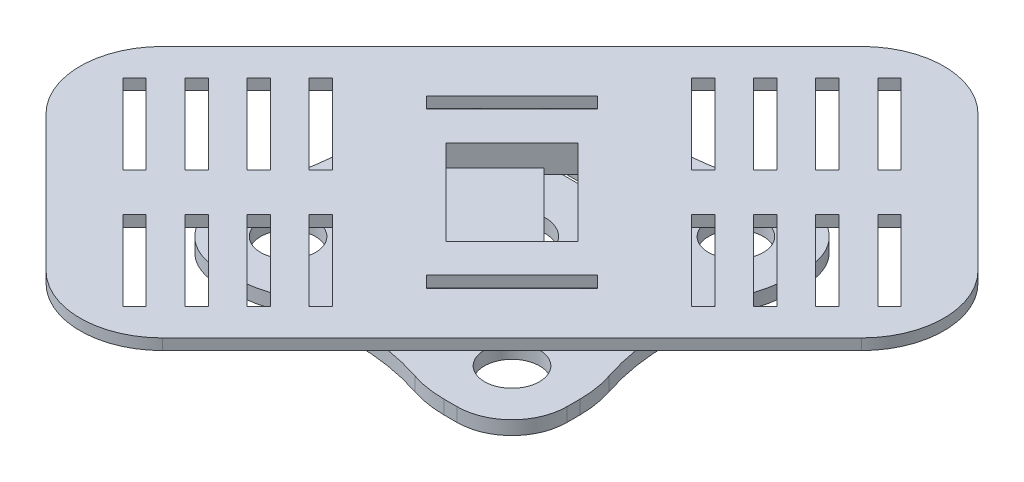
SolidWorks part; units mm, degrees
note: '?' marks a value the reader was unsure of.
ref_plane "Front" through (0, 0, 0) normal (0, 0, 1) x (1, 0, 0)
ref_plane "Top" through (0, 0, 0) normal (0, 1, 0) x (1, 0, 0)
ref_plane "Right" through (0, 0, 0) normal (1, 0, 0) x (0, 0, -1)
sketch "草图1" plane through (0, 0, 0) normal (0, 1, 0) x (1, 0, 0)
  line L0 (0, 24.7487) -> (0, 0) construction
  line L1 (31.8198, -31.8198) -> (15.8406, -31.8198)
  line L2 (31.8198, -31.8198) -> (31.8198, -15.8406)
  line L3 (31.8198, 31.8198) -> (15.8406, 31.8198)
  line L4 (-31.8198, -31.8198) -> (-31.8198, -15.8406)
  line L5 (31.8198, -31.8198) -> (-31.8198, 31.8198) construction
  line L6 (31.8198, 31.8198) -> (-31.8198, -31.8198) construction
  line L7 (0, 24.7487) -> (0, 70.2543) construction
  line L8 (-31.8198, 15.8406) -> (-31.8198, 31.8198)
  line L9 (31.8198, 15.8406) -> (31.8198, 31.8198)
  line L10 (-15.8406, -31.8198) -> (-31.8198, -31.8198)
  line L11 (-15.8406, 31.8198) -> (-31.8198, 31.8198)
  arc A0 (-15.8406, 31.8198) -> (15.8406, 31.8198) centre (0, 70.2543) ccw
  arc A1 (31.8198, 15.8406) -> (31.8198, -15.8406) centre (70.2543, 0) ccw
  arc A2 (15.8406, -31.8198) -> (-15.8406, -31.8198) centre (0, -70.2543) ccw
  arc A3 (-31.8198, -15.8406) -> (-31.8198, 15.8406) centre (-70.2543, 0) ccw
  point P0 (0, 0)
  point P23 (0, 0)
  dimension "D1" = 4
extrude "凸台-拉伸1" add sketch "草图1" along normal blind 2.5
fillet "圆角1" radius 10 1 edges at (31.8198, 1.25, 31.8198)
ref_axis "基准轴1" through (0, 27.9421, 0) along (0, 1, 0)?
fillet "圆角2" radius 10 1 edges at (31.8198, 1.25, -31.8198)
fillet "圆角3" radius 10 1 edges at (-31.8198, 1.25, -31.8198)
fillet "圆角4" radius 10 1 edges at (-31.8198, 1.25, 31.8198)
sketch "草图2" plane through (0, 2.5, 0) normal (0, 1, 0) x (1, 0, 0)
  line L0 (-31.8198, 15.8406) -> (-15.8406, 31.8198) construction
  line L1 (15.8406, -31.8198) -> (31.8198, -15.8406) construction
  line L2 (23.8302, -23.8302) -> (-23.8302, 23.8302) construction
  line L3 (-20.3878, 20.3878) -> (-15.8406, 31.8198) construction
  line L4 (-20.3878, 20.3878) -> (-31.8198, 15.8406) construction
  line L5 (-31.8198, 15.8406) -> (-23.8302, 23.8302) construction
  line L6 (-34.8639, 27.7928) -> (-27.7928, 34.8639) construction
  line L7 (15.8406, 31.8198) -> (-15.8406, 31.8198) construction
  line L12 (0, 31.8198) -> (0, 0) construction
  line L13 (-20.3878, 20.3878) -> (31.8198, 15.8406) construction
  line L14 (-50.7807, 30.9679) -> (-32.266, 49.4825) construction
  line L15 (7.5, 17.2523) -> (-7.5, 17.2523)
  line L16 (7.5, 17.2523) -> (7.5, 14.3647)
  line L17 (7.5, 14.3647) -> (-7.5, 14.3647)
  line L18 (-7.5, 17.2523) -> (-7.5, 14.3647)
  line L19 (7.5, 17.2523) -> (-7.5, 14.3647) construction
  line L20 (7.5, 14.3647) -> (-7.5, 17.2523) construction
  line L21 (-27.7928, 34.8639) -> (-46.8847, 53.9557) construction
  line L22 (-31.3283, 31.3283) -> (0, 0) construction
  line L23 (0, 0) -> (3.5355, 3.5355) construction
  circle A2 centre (-20.3878, 20.3878) radius 5
  circle A3 centre (-46.8847, 53.9557) radius 1.52
  circle A4 centre (-53.9557, 46.8847) radius 1.52
  point P11 (-31.3283, 31.3283)
  point P19 (0, 15.8085)
  dimension "D1" = 44.3049
  dimension "D2" = 28.8327
extrude "切除-拉伸1" cut sketch "草图2" against normal blind 49
fillet "圆角5" radius 20 1 edges at (-15.8406, 1.25, -31.8198)
fillet "圆角6" radius 20 1 edges at (-31.8198, 1.25, -15.8406)
pattern_circular "阵列(圆周)2" count 4 every 90 about axis through (0, 0, 0) along (0, 1, 0) of "切除-拉伸1"
sketch "草图3" plane through (0, 2.5, 0) normal (0, 1, 0) x (1, 0, 0)
  circle A0 centre (0, 0) radius 6
extrude "切除-拉伸2" cut sketch "草图3" against normal blind 49 and the other way blind 85
sketch "草图4" plane through (0, 2.5, 0) normal (0, 1, 0) x (1, 0, 0)
fillet "圆角7" radius 20 1 edges at (31.8198, 1.25, 15.8406)
fillet "圆角8" radius 20 1 edges at (15.8406, 1.25, 31.8198)
fillet "圆角9" radius 20 1 edges at (-31.8198, 1.25, 15.8406)
fillet "圆角10" radius 20 1 edges at (-15.8406, 1.25, 31.8198)
fillet "圆角11" radius 20 1 edges at (15.8406, 1.25, -31.8198)
fillet "圆角12" radius 20 1 edges at (31.8198, 1.25, -15.8406)
ref_plane "基准面1" through (0, 7.5, 0) normal (0, 1, 0) x (1, 0, 0)
sketch "草图5" plane through (0, 7.5, 0) normal (0, 1, 0) x (1, 0, 0)
  line L1 (65.4074, 19.4454) -> (19.4454, 65.4074)
  line L2 (65.4074, 19.4454) -> (-19.4454, -65.4074)
  line L3 (-19.4454, -65.4074) -> (-65.4074, -19.4454)
  line L4 (19.4454, 65.4074) -> (-65.4074, -19.4454)
  line L5 (65.4074, 19.4454) -> (-65.4074, -19.4454) construction
  line L6 (-19.4454, -65.4074) -> (19.4454, 65.4074) construction
  point P0 (0, 0)
extrude "凸台-拉伸2" add sketch "草图5" along normal blind 2 separate body contours L1 L4 L3 L2
sketch "草图6" plane through (0, 7.5, 0) normal (0, 1, 0) x (1, 0, 0)
  line L0 (-24.3496, 0) -> (0, 0) construction
  line L1 (-22.8496, 6.8283) -> (-25.8496, 6.8283)
  line L2 (-22.8496, 6.8283) -> (-22.8496, -6.8283)
  line L3 (-22.8496, -6.8283) -> (-25.8496, -6.8283)
  line L4 (-25.8496, 6.8283) -> (-25.8496, -6.8283)
  line L5 (-22.8496, 6.8283) -> (-25.8496, -6.8283) construction
  line L6 (-22.8496, -6.8283) -> (-25.8496, 6.8283) construction
  line L7 (-6.8283, 22.8496) -> (-6.8283, 25.8496)
  line L8 (6.8283, 22.8496) -> (-6.8283, 22.8496)
  line L9 (6.8283, 25.8496) -> (-6.8283, 25.8496)
  line L10 (6.8283, 22.8496) -> (6.8283, 25.8496)
  line L11 (22.8496, 6.8283) -> (25.8496, 6.8283)
  line L12 (22.8496, -6.8283) -> (22.8496, 6.8283)
  line L13 (25.8496, -6.8283) -> (25.8496, 6.8283)
  line L14 (22.8496, -6.8283) -> (25.8496, -6.8283)
  line L15 (6.8283, -22.8496) -> (6.8283, -25.8496)
  line L16 (-6.8283, -22.8496) -> (6.8283, -22.8496)
  line L17 (-6.8283, -25.8496) -> (6.8283, -25.8496)
  line L18 (-6.8283, -22.8496) -> (-6.8283, -25.8496)
  point P0 (-24.3496, 0)
  point P23 (0, 0)
  dimension "D1" = 4
extrude "凸台-拉伸3" add sketch "草图6" against normal up to next
fillet "圆角13" radius 15 1 edges at (65.4074, 8.5, -19.4454)
fillet "圆角14" radius 15 1 edges at (19.4454, 8.5, -65.4074)
fillet "圆角15" radius 15 1 edges at (-19.4454, 8.5, 65.4074)
fillet "圆角16" radius 15 1 edges at (-65.4074, 8.5, 19.4454)
sketch "草图7" plane through (0, 9.5, 0) normal (0, 1, 0) x (1, 0, 0)
  line L0 (53.4337, 17.4298) -> (38.9664, 31.8972)
  line L13 (53.4337, 17.4298) -> (51.3124, 15.3085)
  line L14 (38.9664, 31.8972) -> (36.8451, 29.7758)
  line L15 (51.3124, 15.3085) -> (36.8451, 29.7758)
  line L16 (53.4337, 17.4298) -> (36.8451, 29.7758) construction
  line L17 (38.9664, 31.8972) -> (51.3124, 15.3085) construction
  line L18 (54.8008, 30.052) -> (30.052, 54.8008) construction
  line L19 (0, 0) -> (48.166, 48.166) construction
  line L20 (0, 0) -> (-36.2666, 36.2666) construction
  line L21 (31.8972, 38.9664) -> (15.3085, 51.3124) construction
  line L22 (17.4298, 53.4337) -> (29.7758, 36.8451) construction
  line L23 (15.3085, 51.3124) -> (29.7758, 36.8451)
  line L24 (31.8972, 38.9664) -> (29.7758, 36.8451)
  line L25 (17.4298, 53.4337) -> (15.3085, 51.3124)
  line L26 (17.4298, 53.4337) -> (31.8972, 38.9664)
  point P4 (45.1394, 23.6028)
  point P16 (23.6028, 45.1394)
extrude "切除-拉伸3" cut sketch "草图7" against normal blind 2
sketch "草图8" plane through (0, 9.5, 0) normal (0, 1, 0) x (1, 0, 0)
  line L0 (-23.7289, -23.7289) -> (16.7245, 16.7245) construction
  line L1 (0, 0) -> (-14.1421, 14.1421) construction
  line L2 (-7.4246, 22.981) -> (-22.981, 7.4246)
  line L3 (-7.4246, 22.981) -> (-5.3033, 20.8597)
  line L4 (-22.981, 7.4246) -> (-20.8597, 5.3033)
  line L5 (-5.3033, 20.8597) -> (-20.8597, 5.3033)
  line L6 (-7.4246, 22.981) -> (-20.8597, 5.3033) construction
  line L7 (-22.981, 7.4246) -> (-5.3033, 20.8597) construction
  line L8 (7.4246, -22.981) -> (20.8597, -5.3033) construction
  line L9 (22.981, -7.4246) -> (5.3033, -20.8597) construction
  line L10 (20.8597, -5.3033) -> (5.3033, -20.8597)
  line L11 (7.4246, -22.981) -> (5.3033, -20.8597)
  line L12 (22.981, -7.4246) -> (20.8597, -5.3033)
  line L13 (22.981, -7.4246) -> (7.4246, -22.981)
pattern_linear "阵列(线性)1" count 4 spacing 8 along (-0.7071, 0, 0.7071) of "切除-拉伸3"
ref_plane "基准面2" through (0, 0, 0) normal (0.7071, 0, -0.7071) x (-0.7071, 0, -0.7071)
mirror "镜向1" about plane through (0, 0, 0) normal (0.7071, 0, -0.7071) of "阵列(线性)1", "切除-拉伸3"
extrude "切除-拉伸4" cut sketch "草图8" against normal blind 2
sketch "草图9" plane through (0, 9.5, 0) normal (0, 1, 0) x (1, 0, 0)
  line L9 (13.7886, -1.7678) -> (-1.7678, 13.7886)
  line L10 (13.7886, -1.7678) -> (1.7678, -13.7886)
  line L11 (1.7678, -13.7886) -> (-13.7886, 1.7678)
  line L12 (-1.7678, 13.7886) -> (-13.7886, 1.7678)
  line L13 (13.7886, -1.7678) -> (-13.7886, 1.7678) construction
  line L14 (1.7678, -13.7886) -> (-1.7678, 13.7886) construction
  point P0 (0, 0)
sketch "草图11" plane through (0, 9.5, 0) normal (0, 1, 0) x (1, 0, 0)
  line L1 (-15.9099, 1.7678) -> (1.7678, -15.9099)
  line L2 (-15.9099, 1.7678) -> (-1.7678, 15.9099)
  line L3 (-1.7678, 15.9099) -> (15.9099, -1.7678)
  line L4 (1.7678, -15.9099) -> (15.9099, -1.7678)
  line L5 (-15.9099, 1.7678) -> (15.9099, -1.7678) construction
  line L6 (-1.7678, 15.9099) -> (1.7678, -15.9099) construction
  point P0 (0, 0)
extrude "凸台-拉伸4" add sketch "草图11" against normal blind 5
extrude "切除-拉伸5" cut sketch "草图9" against normal blind 4
sketch "草图12" plane through (0, 5.5, 0) normal (0, 1, 0) x (1, 0, 0)
  line L5 (-1.7678, 13.7886) -> (-13.7886, 1.7678) construction
  line L6 (-4.8435, 10.7128) -> (-1.7191, 13.8372)
  line L7 (-4.8435, 10.7128) -> (10.7128, -4.8435)
  line L8 (10.7128, -4.8435) -> (13.8372, -1.7191)
  line L9 (-1.7191, 13.8372) -> (13.8372, -1.7191)
  line L10 (1.7678, -13.7886) -> (13.7886, -1.7678) construction
extrude "切除-拉伸6" cut sketch "草图12" against normal blind 2
